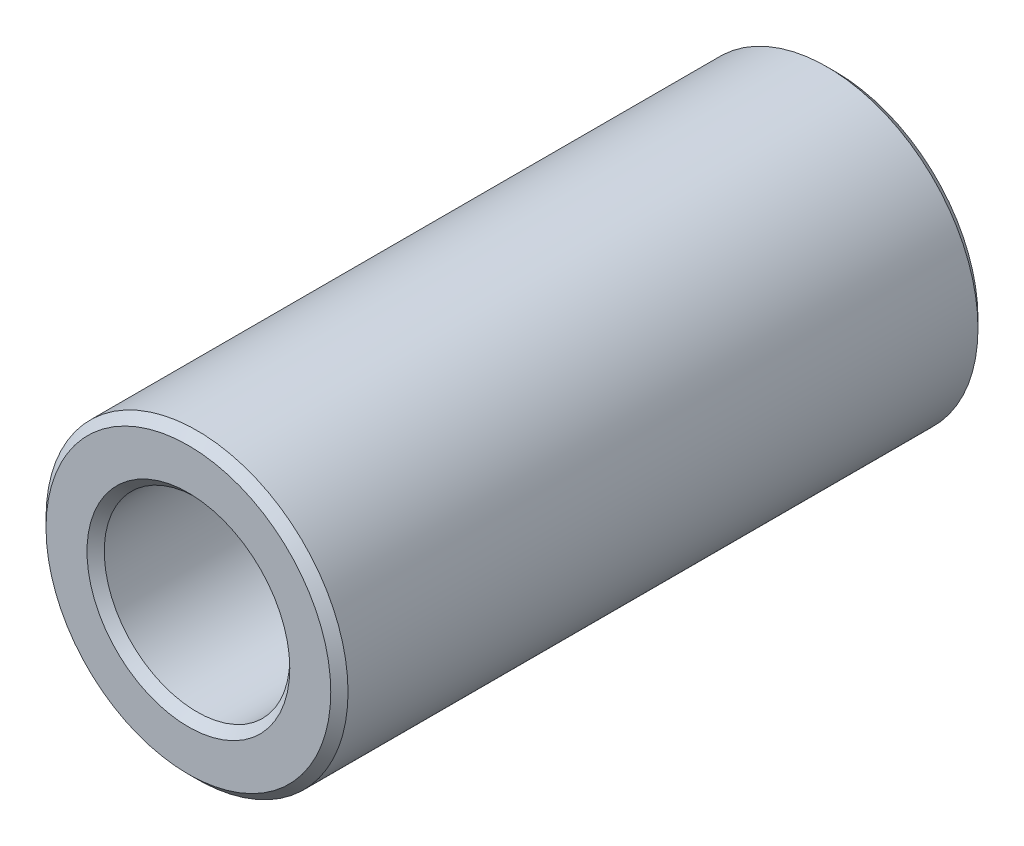
SolidWorks part; units mm, degrees
material "ABS"
ref_plane "Front" through (0, 0, 0) normal (0, 0, 1) x (1, 0, 0)
ref_plane "Top" through (0, 0, 0) normal (0, 1, 0) x (1, 0, 0)
ref_plane "Right" through (0, 0, 0) normal (1, 0, 0) x (0, 0, -1)
sketch "Эскиз1" plane through (0, 0, 0) normal (0, 0, 1) x (1, 0, 0)
  circle A0 centre (0, 0) radius 2.15
  circle A1 centre (0, 0) radius 3.5
  dimension "D1" = 4.3
  dimension "D2" = 7
extrude "Бобышка-Вытянуть1" add sketch "Эскиз1" along normal blind 15
chamfer "Фаска1" distance 0.2 angle 45 4 edges at (2.15, 0, 0) (3.5, 0, 0) (2.15, 0, 15) (3.5, 0, 15)
